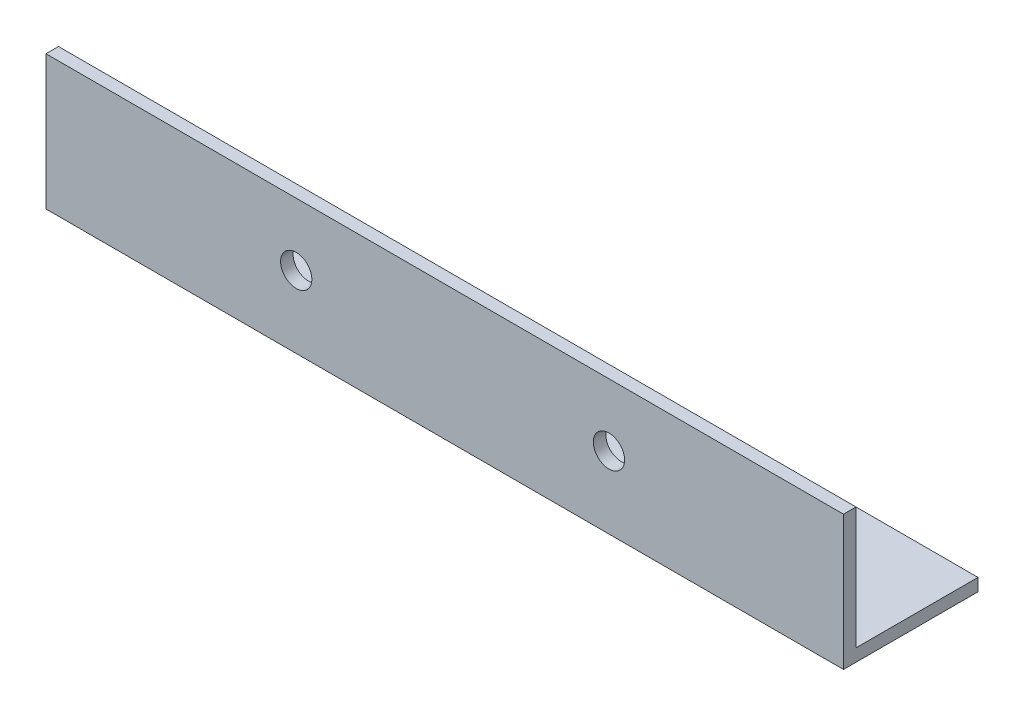
SolidWorks part; units mm, degrees
ref_plane "Спереди" through (0, 0, 0) normal (0, 0, 1) x (1, 0, 0)
ref_plane "Сверху" through (0, 0, 0) normal (0, 1, 0) x (1, 0, 0)
ref_plane "Справа" through (0, 0, 0) normal (1, 0, 0) x (0, 0, -1)
sketch "Эскиз1" plane through (0, 0, 0) normal (1, 0, 0) x (0, 0, -1)
  line L0 (0, 43) -> (0, 0)
  line L1 (0, 0) -> (43, 0)
extrude "Вытянуть-Тонкостенный1" add sketch "Эскиз1" along normal blind 255 thin thin type one direction reverse wall 4
sketch "Эскиз2" plane through (0, 0, 0) normal (0, 0, 1) x (1, 0, 0)
  circle A0 centre (80, 23) radius 5
  circle A1 centre (180, 23) radius 5
  dimension "D1" = 2
extrude "Вырез-Вытянуть1" cut sketch "Эскиз2" against normal through all
